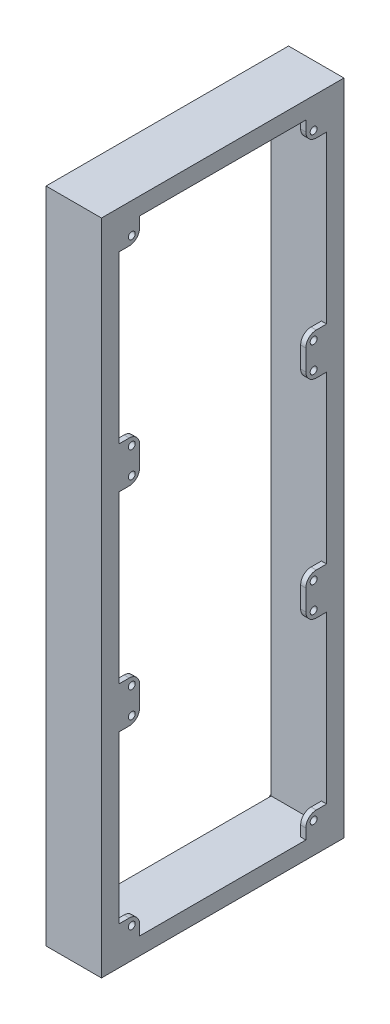
SolidWorks part; units mm, degrees
ref_plane "Front Plane" through (0, 0, 0) normal (1, 0, 0) x (0, 1, 0)
ref_plane "Top Plane" through (0, 0, 0) normal (0, 0, 1) x (0, 1, 0)
ref_plane "Right Plane" through (0, 0, 0) normal (0, 1, 0) x (-1, 0, 0)
sketch "Sketch1" plane through (0, 0, 0) normal (1, 0, 0) x (0, 1, 0)
  line L0 (-60, 60) -> (-60, -60) construction
  line L1 (-180, -60) -> (180, -60)
  line L2 (-180, -60) -> (-180, 60)
  line L3 (-180, 60) -> (180, 60)
  line L4 (180, -60) -> (180, 60)
  line L5 (-180, -60) -> (180, 60) construction
  line L6 (-180, 60) -> (180, -60) construction
  line L7 (60, 60) -> (60, -60.0055) construction
  line L8 (-180, -60) -> (-60, 60) construction
  line L9 (-72, 60) -> (-60, 60)
  line L10 (-180, 48) -> (-174, 48)
  line L11 (-180, 48) -> (-180, 60)
  line L12 (-180, 60) -> (-168, 60)
  line L13 (-168, 54) -> (-168, 60)
  line L14 (-72, 60) -> (-72, 54)
  line L15 (-66, 48) -> (-60, 48)
  line L16 (-60, 60) -> (-60, 48)
  line L17 (-60, -48) -> (-60, -60)
  line L18 (-60, -48) -> (-66, -48)
  line L19 (-72, -54) -> (-72, -60)
  line L20 (-60, -60) -> (-72, -60)
  line L21 (-168, -60) -> (-180, -60)
  line L22 (-168, -60) -> (-168, -54)
  line L23 (-174, -48) -> (-180, -48)
  line L24 (-180, -60) -> (-180, -48)
  line L25 (-60, 48) -> (-60, 60)
  line L26 (-60, 48) -> (-54, 48)
  line L27 (-48, 54) -> (-48, 60)
  line L28 (-60, 60) -> (-48, 60)
  line L29 (-48, -60) -> (-60, -60)
  line L30 (-60, -60) -> (-60, -48)
  line L31 (-54, -48) -> (-60, -48)
  line L32 (-48, -60) -> (-48, -54)
  line L33 (60, -48) -> (60, -60)
  line L34 (60, -60) -> (48, -60)
  line L35 (48, -54) -> (48, -60)
  line L36 (60, -48) -> (54, -48)
  line L37 (48, 60) -> (60, 60)
  line L38 (60, 60) -> (60, 48)
  line L39 (54, 48) -> (60, 48)
  line L40 (48, 60) -> (48, 54)
  line L41 (60, 48) -> (60, 60)
  line L42 (60, 48) -> (66, 48)
  line L43 (72, 54) -> (72, 60)
  line L44 (60, 60) -> (72, 60)
  line L45 (72, -60) -> (60, -60)
  line L46 (60, -60) -> (60, -48)
  line L47 (66, -48) -> (60, -48)
  line L48 (72, -60) -> (72, -54)
  line L49 (180, -48) -> (180, -60)
  line L50 (180, -60) -> (168, -60)
  line L51 (168, -54) -> (168, -60)
  line L52 (180, -48) -> (174, -48)
  line L53 (168, 60) -> (180, 60)
  line L54 (180, 60) -> (180, 48)
  line L55 (174, 48) -> (180, 48)
  line L56 (168, 60) -> (168, 54)
  line L57 (-180, 48) -> (-60, 48) construction
  line L59 (-190, 70) -> (190, 70)
  line L60 (-190, 70) -> (-190, -70)
  line L61 (-190, -70) -> (190, -70)
  line L62 (190, 70) -> (190, -70)
  line L63 (-190, 70) -> (190, -70) construction
  line L64 (-190, -70) -> (190, 70) construction
  circle A0 centre (-172.5, 52.5) radius 2
  arc A1 (-174, 48) -> (-168, 54) centre (-174, 54) ccw
  arc A2 (-72, 54) -> (-66, 48) centre (-66, 54) ccw
  circle A3 centre (-67.5, 52.5) radius 2
  arc A4 (-66, -48) -> (-72, -54) centre (-66, -54) ccw
  circle A5 centre (-67.5, -52.5) radius 2
  arc A6 (-168, -54) -> (-174, -48) centre (-174, -54) ccw
  circle A7 centre (-172.5, -52.5) radius 2
  arc A8 (-54, 48) -> (-48, 54) centre (-54, 54) ccw
  circle A9 centre (-52.5, 52.5) radius 2
  circle A10 centre (-52.5, -52.5) radius 2
  arc A11 (-48, -54) -> (-54, -48) centre (-54, -54) ccw
  arc A12 (54, -48) -> (48, -54) centre (54, -54) ccw
  circle A13 centre (52.5, -52.5) radius 2
  arc A14 (48, 54) -> (54, 48) centre (54, 54) ccw
  circle A15 centre (52.5, 52.5) radius 2
  arc A16 (66, 48) -> (72, 54) centre (66, 54) ccw
  circle A17 centre (67.5, 52.5) radius 2
  circle A18 centre (67.5, -52.5) radius 2
  arc A19 (72, -54) -> (66, -48) centre (66, -54) ccw
  arc A20 (174, -48) -> (168, -54) centre (174, -54) ccw
  circle A21 centre (172.5, -52.5) radius 2
  arc A22 (168, 54) -> (174, 48) centre (174, 54) ccw
  circle A23 centre (172.5, 52.5) radius 2
  point P0 (0, 0)
  point P12 (-60, 0)
  point P16 (-120, 0)
  point P18 (-177, 48)
  point P19 (-168, 57)
  point P22 (-168, 48)
  point P24 (0, 0)
  dimension "D3" = 4
  dimension "D5" = 105
  dimension "D8" = 6
  dimension "D1" = 360
  dimension "D2" = 120
  dimension "D4" = 7.5
  dimension "D6" = 120
  dimension "D7" = 12
  dimension "D9" = 120
  dimension "D10" = 4
  dimension "D11" = 3
  dimension "D12" = 120
  dimension "D13" = 10
  dimension "D14" = 10
extrude "Boss-Extrude2" add sketch "Sketch1" along normal blind 3 contours L62 L59 L60 L61 L4 L1 L2 L3 | L10 A1 L13 L3 L2 A0 | L14 A2 L15 L16 L3 A3 | L26 A8 L27 L3 L16 A9 | L32 A11 L31 L17 L1 A10 | L18 A4 L19 L1 L17 A5 | L22 A6 L23 L2 L1 A7 | L36 A12 L35 L1 L33 A13 | L48 A19 L47 L33 L1 A18 | L42 A16 L43 L3 L38 A17 | L40 A14 L39 L38 L3 A15 | L56 A22 L55 L4 L3 A23 | L52 A20 L51 L1 L4 A21 region at (0, -174.4434, -54.4434) region at (0, -65.5566, -54.4434) region at (0, -174.4434, 54.4434) region at (0, -54.4434, -54.4434) region at (0, 54.4434, -54.4434) region at (0, -65.5566, 54.4434) region at (0, 65.5566, -54.4434) region at (0, -54.4434, 54.4434) region at (0, 174.4434, -54.4434) region at (0, 54.4434, 54.4434) region at (0, 65.5566, 54.4434) region at (0, 174.4434, 54.4434) region at (0, 0, 65.9503)
extrude "Boss-Extrude5" add sketch "Sketch1<6>" against normal blind 29 contours L62 L59 L60 L61 L4 L1 L2 L3 region at (0, 0, 65.9503)
sketch "Sketch1<6>" plane through (0, 0, 0) normal (1, 0, 0) x (0, 1, 0) same geometry as "Sketch1"
sketch "Sketch14" plane through (-29, 0, 0) normal (-1, 0, 0) x (0, -1, 0)
  line L0 (-190, 70) -> (-180, 60) construction
  line L1 (0, 0) -> (-50000, 0) construction
  line L2 (-190, 70) -> (-190, -70) construction
  line L3 (0, 0) -> (0, -50000) construction
  line L4 (180, -60) -> (-180, -60) construction
  line L5 (190, 70) -> (-190, 70) construction
  line L6 (-189, 69) -> (189, 69)
  line L7 (-189, 69) -> (-189, -69)
  line L8 (-189, -69) -> (189, -69)
  line L9 (189, 69) -> (189, -69)
  line L10 (-188.6, 68.6) -> (188.6, 68.6)
  line L11 (188.6, 68.6) -> (188.6, -68.6)
  line L12 (-188.6, -68.6) -> (188.6, -68.6)
  line L13 (-188.6, 68.6) -> (-188.6, -68.6)
  line L14 (190, 70) -> (190, -70) construction
  line L15 (190, -70) -> (-190, -70) construction
  circle A0 centre (-182.9289, 62.9289) radius 3.15
  circle A1 centre (-182.9289, 62.9289) radius 3.95
  circle A2 centre (182.9289, 62.9289) radius 3.15
  circle A3 centre (182.9289, 62.9289) radius 3.95
  circle A4 centre (182.9289, -62.9289) radius 3.15
  circle A5 centre (182.9289, -62.9289) radius 3.95
  circle A6 centre (-182.9289, -62.9289) radius 3.95
  circle A7 centre (-182.9289, -62.9289) radius 3.15
  point P13 (-190, 0)
  point P18 (0, -60)
  dimension "D1" = 6.3
  dimension "D3" = 1
  dimension "D4" = 0.4
  dimension "D5" = 1
  dimension "D6" = 1
  dimension "D7" = 10
  dimension "D2" = 0.8
extrude "Boss-Extrude7" add sketch "Sketch14" along normal blind 0.2 contours L7 L8 L9 L6 | L13 L12 L11 L10
extrude "Boss-Extrude9" add sketch "Sketch14<4>" along normal blind 0.8 contours A1 | A3 | A5 | A6
sketch "Sketch14<4>" plane through (-29, 0, 0) normal (-1, 0, 0) x (0, -1, 0) same geometry as "Sketch14"
extrude "Mounting magnet holes" cut sketch "Sketch14<5>" along normal blind 0.6 and the other way blind 1.5 contours A0 | A7 | A4 | A2
sketch "Sketch14<5>" plane through (-29, 0, 0) normal (-1, 0, 0) x (0, -1, 0) same geometry as "Sketch14"
sketch "Sketch17" plane through (-29.2, 0, 0) normal (-1, 0, 0) x (0, -1, 0)
  line L10 (-188.6, 68.6) -> (188.6, 68.6)
  line L11 (-188.6, 68.6) -> (-188.6, -68.6)
  line L12 (189.2, 69.2) -> (-189.2, 69.2)
  line L13 (-189.2, 69.2) -> (-189.2, -69.2)
  line L14 (-189.2, -69.2) -> (189.2, -69.2)
  line L15 (189.2, -69.2) -> (189.2, 69.2)
  line L16 (189.2, 69.2) -> (-189.2, 69.2)
  line L17 (-189.2, 69.2) -> (-189.2, -69.2)
  line L18 (-189.2, -69.2) -> (189.2, -69.2)
  line L19 (189.2, -69.2) -> (189.2, 69.2)
  line L20 (-188.6, -68.6) -> (188.6, -68.6)
  line L21 (188.6, 68.6) -> (188.6, -68.6)
  dimension "D1" = 0.2
extrude "Boss-Extrude10" add sketch "Sketch17" along normal blind 0.4
chamfer "Chamfer1" distance 0.4 angle 30 4 edges at (-29.6, 0, -69.2) (-29.6, -189.2, 0) (-29.6, 189.2, 0) (-29.6, 0, 69.2) first distance on face at (-29.4, 0, -69.2) first distance on face at (-29.4, -189.2, 0) first distance on face at (-29.4, 189.2, 0) first distance on face at (-29.4, 0, 69.2)
sketch "Sketch18" plane through (3, 0, 0) normal (1, 0, 0) x (0, 1, 0)
  line L0 (-190, 70) -> (190, 70) construction
  line L1 (-190, 70) -> (-190, -70) construction
  line L2 (0, 0) -> (-358.4227, 0) construction
  line L3 (0, 0) -> (0, 85.8788) construction
  circle A0 centre (-185, 65) radius 3.15
  circle A2 centre (185, 65) radius 3.15
  circle A4 centre (185, -65) radius 3.15
  circle A7 centre (-185, -65) radius 3.15
  dimension "D1" = 6.3
  dimension "D2" = 5
  dimension "D3" = 5
  dimension "D4" = 6.3
extrude "Cover magnet holes" cut sketch "Sketch18" against normal blind 2.1 from offset 0.4 offset against normal yes
